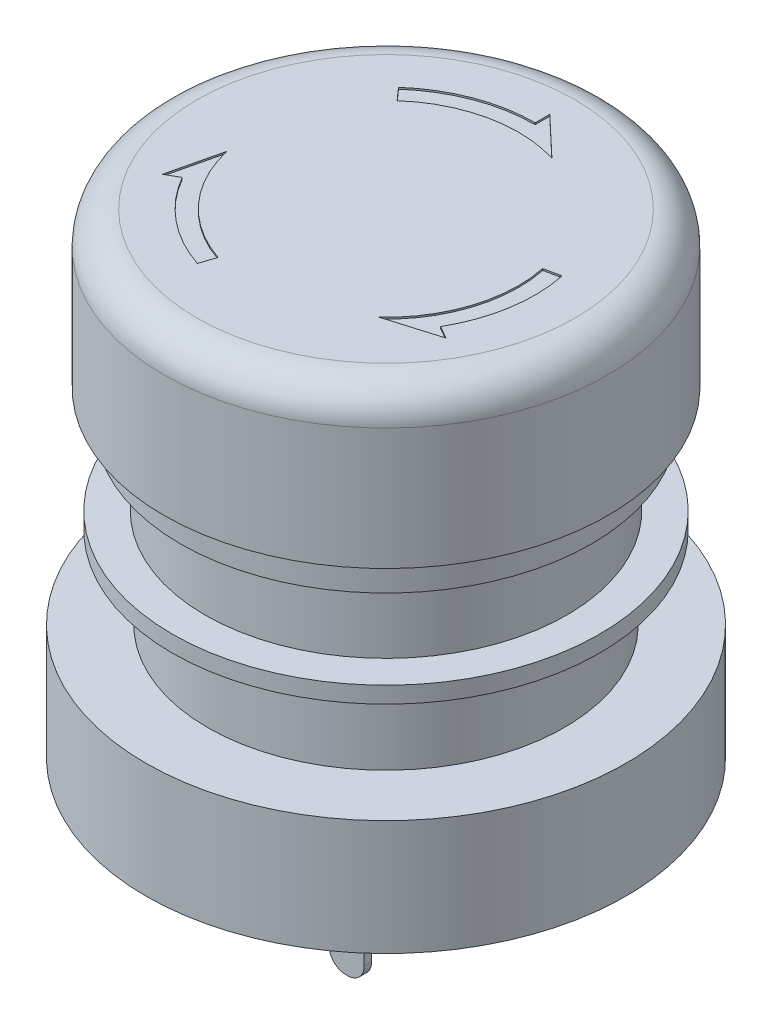
SolidWorks part; units mm, degrees
ref_plane "前视基准面" through (0, 0, 0) normal (0, 0, 1) x (1, 0, 0)
ref_plane "上视基准面" through (0, 0, 0) normal (0, 1, 0) x (1, 0, 0)
ref_plane "右视基准面" through (0, 0, 0) normal (1, 0, 0) x (0, 0, -1)
sketch "草图1" plane through (0, 0, 0) normal (0, 1, 0) x (1, 0, 0)
  circle A0 centre (0, 0) radius 7.5
  dimension "D1" = 15
extrude "凸台-拉伸1" add sketch "草图1" along normal blind 2
sketch "草图2" plane through (0, 0, 0) normal (0, -1, 0) x (1, 0, 0)
  line L0 (0, 0) -> (0, 7.5) construction
  line L1 (-4.2318, 5.5619) -> (-2.1076, 5.5619)
  line L2 (-4.2318, 5.5619) -> (-4.2318, 5.1067)
  line L3 (-4.2318, 5.1067) -> (-2.1076, 5.1067)
  line L4 (-2.1076, 5.5619) -> (-2.1076, 5.1067)
  line L5 (-4.2318, 5.5619) -> (-2.1076, 5.1067) construction
  line L6 (-4.2318, 5.1067) -> (-2.1076, 5.5619) construction
  line L7 (0, 0) -> (-7.5, 0) construction
  line L8 (4.2318, 5.1067) -> (2.1076, 5.5619) construction
  line L9 (4.2318, 5.5619) -> (2.1076, 5.1067) construction
  line L10 (2.1076, 5.5619) -> (2.1076, 5.1067)
  line L11 (4.2318, 5.1067) -> (2.1076, 5.1067)
  line L12 (4.2318, 5.5619) -> (4.2318, 5.1067)
  line L13 (4.2318, 5.5619) -> (2.1076, 5.5619)
  line L14 (4.2318, -5.5619) -> (2.1076, -5.1067) construction
  line L15 (4.2318, -5.1067) -> (2.1076, -5.5619) construction
  line L16 (4.2318, -5.5619) -> (2.1076, -5.5619)
  line L17 (4.2318, -5.5619) -> (4.2318, -5.1067)
  line L18 (2.1076, -5.5619) -> (2.1076, -5.1067)
  line L19 (-4.2318, -5.1067) -> (-2.1076, -5.5619) construction
  line L20 (-4.2318, -5.5619) -> (-2.1076, -5.1067) construction
  line L21 (-2.1076, -5.5619) -> (-2.1076, -5.1067)
  line L22 (-4.2318, -5.5619) -> (-4.2318, -5.1067)
  line L23 (-4.2318, -5.5619) -> (-2.1076, -5.5619)
  line L24 (4.2318, -5.1067) -> (2.1076, -5.1067)
  line L25 (-4.2318, -5.1067) -> (-2.1076, -5.1067)
  circle A0 centre (0, 0) radius 7.5 construction
  point P0 (-3.1697, 5.3343)
  point P16 (3.1697, 5.3343)
  point P21 (3.1697, -5.3343)
  point P26 (-3.1697, -5.3343)
extrude "凸台-拉伸2" add sketch "草图2" along normal blind 3.5
fillet "圆角1" radius 1 8 edges at (-4.2318, -3.5, -5.3343) (-2.1076, -3.5, -5.3343) (2.1076, -3.5, -5.3343) (4.2318, -3.5, -5.3343) (4.2318, -3.5, 5.3343) (2.1076, -3.5, 5.3343) (-2.1076, -3.5, 5.3343) (-4.2318, -3.5, 5.3343)
sketch "草图4" plane through (0, 2, 0) normal (0, 1, 0) x (1, 0, 0)
  circle A0 centre (0, 0) radius 10.85
  dimension "D1" = 21.7
extrude "凸台-拉伸3" add sketch "草图4" along normal blind 8.6
sketch "草图5" plane through (0, 10.6, 0) normal (0, 1, 0) x (1, 0, 0)
  circle A1 centre (0, 0) radius 13
  dimension "D1" = 26
extrude "凸台-拉伸4" add sketch "草图5" along normal blind 6
sketch "草图7" plane through (0, 16.6, 0) normal (0, 1, 0) x (1, 0, 0)
  circle A0 centre (0, 0) radius 11
  dimension "D1" = 22
extrude "凸台-拉伸6" add sketch "草图7" along normal blind 4.5
sketch "草图8" plane through (0, 21.1, 0) normal (0, 1, 0) x (1, 0, 0)
  circle A0 centre (0, 0) radius 13.5
  dimension "D1" = 27
extrude "凸台-拉伸7" add sketch "草图8" along normal blind 11.4
fillet "圆角5" radius 2 1 edges at (0, 32.5, 13.5)
sketch "草图9" plane through (0, 21.1, 0) normal (0, -1, 0) x (1, 0, 0)
  circle A0 centre (0, 0) radius 12.5
  dimension "D1" = 25
extrude "切除-拉伸1" cut sketch "草图9" against normal blind 2 flip side to cut
sketch "草图10" plane through (0, 32.5, 0) normal (0, 1, 0) x (1, 0, 0)
  line L0 (0, 9.0737) -> (0, 9.9619)
  line L1 (0, 9.9619) -> (2.376, 7.7162)
  line L2 (-5.3606, 6.0373) -> (-6.0245, 6.7851)
  line L3 (8.6273, -4.981) -> (5.4944, -5.9158)
  line L4 (7.8581, -4.5369) -> (8.6273, -4.981)
  line L5 (7.9088, 1.6237) -> (8.8883, 1.8248)
  line L6 (-8.6273, -4.981) -> (-7.8704, -1.8004)
  line L7 (-7.8581, -4.5369) -> (-8.6273, -4.981)
  line L8 (-2.5482, -7.661) -> (-2.8638, -8.6099)
  arc A0 (2.376, 7.7162) -> (-5.3606, 6.0373) centre (0, 0) ccw
  arc A1 (0, 9.0737) -> (-6.0245, 6.7851) centre (0, 0) ccw
  circle A2 centre (0, 0) radius 8.0737 construction
  circle A3 centre (0, 0) radius 9.0737 construction
  arc A4 (5.4944, -5.9158) -> (7.9088, 1.6237) centre (0, 0) ccw
  arc A5 (7.8581, -4.5369) -> (8.8883, 1.8248) centre (0, 0) ccw
  arc A6 (-7.8704, -1.8004) -> (-2.5482, -7.661) centre (0, 0) ccw
  arc A7 (-7.8581, -4.5369) -> (-2.8638, -8.6099) centre (0, 0) ccw
  point P22 (0, 0)
  dimension "D1" = 1
  dimension "D2" = 3
extrude "切除-拉伸2" cut sketch "草图10" against normal blind 0.1
sketch "草图11" plane through (0, 10.6, 0) normal (0, -1, 0) x (1, 0, 0)
  circle A0 centre (0, 0) radius 14.605
  dimension "D1" = 29.21
extrude "凸台-拉伸8" add sketch "草图11" along normal blind 7
sketch "草图12" plane through (0, 10.6, 0) normal (0, 1, 0) x (1, 0, 0)
  circle A0 centre (0, 0) radius 13 construction
  circle A1 centre (0, 0) radius 13
  circle A2 centre (0, 0) radius 10.85 construction
  circle A3 centre (0, 0) radius 10.85
extrude "切除-拉伸3" cut sketch "草图12" along normal offset from surface (5 mm away) 1 up to face at (0, 16.6, 11)
sketch "草图13" plane through (0, -3.5, 0) normal (0, -1, 0) x (1, 0, 0)
  point P0 (-3.1697, 5.3377)
  point P1 (-3.1697, -5.3343)
  point P2 (3.1697, 5.3377)
other "连接点1" parameters "直径"=2, "端头长度"=1
ref_axis "基准轴1" through (-3.1697, -13.5, 5.3377) along (0, 1, 0)
other "连接点2" parameters "直径"=2, "端头长度"=1
ref_axis "基准轴2" through (-3.1697, -13.5, -5.3343) along (0, 1, 0)
